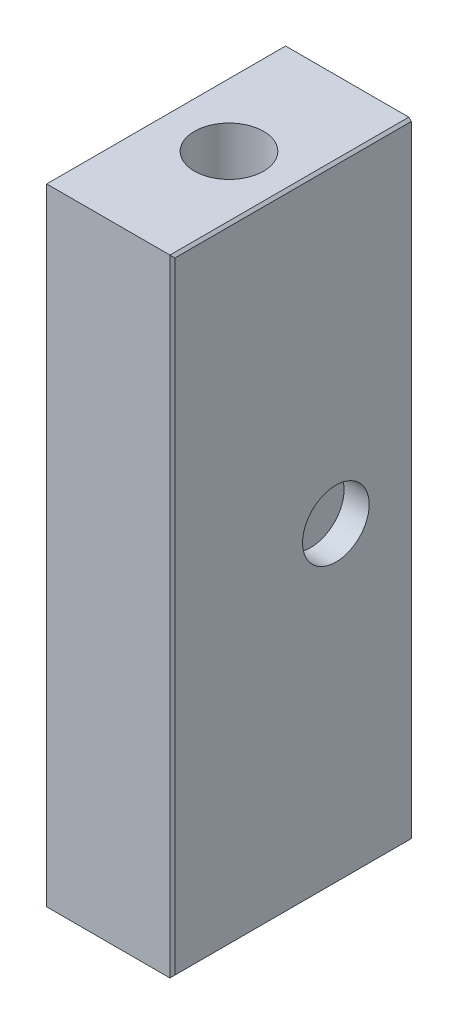
SolidWorks part; units mm, degrees
material "ABS"
ref_plane "Front Plane" through (0, 0, 0) normal (0, 0, 1) x (1, 0, 0)
ref_plane "Top Plane" through (0, 0, 0) normal (0, 1, 0) x (1, 0, 0)
ref_plane "Right Plane" through (0, 0, 0) normal (1, 0, 0) x (0, 0, -1)
sketch "Sketch1" plane through (0, 0, 0) normal (0, 1, 0) x (1, 0, 0)
  line L6 (5, -9.5) -> (-5, -9.5)
  line L9 (5, -9.5) -> (5, 9.5)
  line L10 (5, 9.5) -> (-5, 9.5)
  line L11 (-5, -9.5) -> (-5, 9.5)
  line L13 (5, -9.5) -> (-5, 9.5) construction
  line L14 (5, 9.5) -> (-5, -9.5) construction
  circle A2 centre (0, 0) radius 2.75
  point P0 (0, 0)
  point P7 (0, 0)
  point P8 (0, 0)
  point P9 (0, 0)
  dimension "D2" = 5.5
  dimension "D1" = 10
  dimension "D3" = 19
extrude "Boss-Extrude1" add sketch "Sketch1" along normal mid plane 49.8
sketch "Sketch2" plane through (5, 0, 0) normal (1, 0, 0) x (0, 0, -1)
  line L3 (-9.5, -25) -> (-9.5, 25) construction
  circle A0 centre (3.5, 0) radius 2.65
  dimension "D1" = 5.3
  dimension "D2" = 13
extrude "Cut-Extrude1" cut sketch "Sketch2" against normal blind 2
chamfer "Chamfer1" distance 0.2 angle 45 3 edges at (5, -24.9, 0) (5, 0, 9.5) (5, 24.9, 0)
